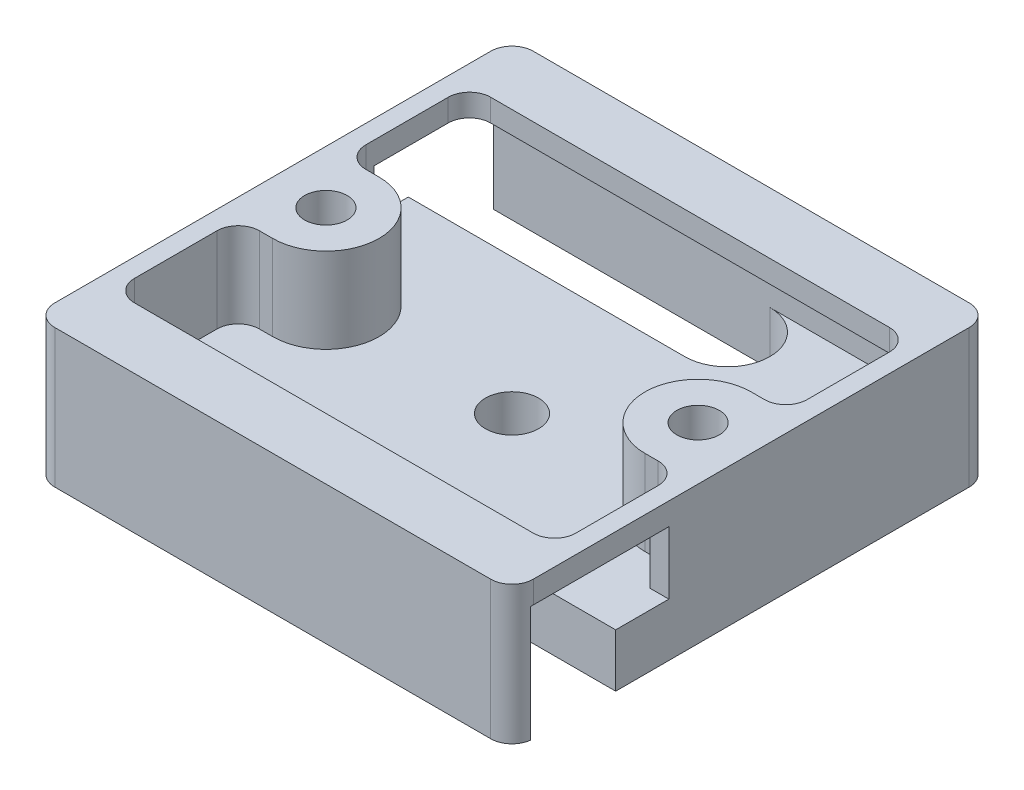
SolidWorks part; units mm, degrees
material "ABS PC"
ref_plane "Alzado" through (0, 0, 0) normal (0, 0, 1) x (1, 0, 0)
ref_plane "Planta" through (0, 0, 0) normal (0, 1, 0) x (1, 0, 0)
ref_plane "Vista lateral" through (0, 0, 0) normal (1, 0, 0) x (0, 0, -1)
sketch "Croquis1" plane through (0, 0, 0) normal (0, 1, 0) x (1, 0, 0)
  line L0 (22.5, -16.75) -> (-3.5, -16.75) construction
  line L1 (-18.5, -18.5) -> (18.5, -18.5) construction
  line L2 (-18.5, -18.5) -> (-18.5, 18.5) construction
  line L3 (-18.5, 18.5) -> (18.5, 18.5) construction
  line L4 (18.5, -18.5) -> (18.5, 18.5) construction
  line L5 (-18.5, -18.5) -> (18.5, 18.5) construction
  line L6 (-18.5, 18.5) -> (18.5, -18.5) construction
  line L7 (-20.75, -20.75) -> (20.75, -20.75) construction
  line L8 (-20.75, -20.75) -> (-20.75, 20.75) construction
  line L9 (-20.75, 20.75) -> (20.75, 20.75) construction
  line L10 (20.75, -20.75) -> (20.75, 20.75) construction
  line L11 (-20.75, -20.75) -> (20.75, 20.75) construction
  line L12 (-20.75, 20.75) -> (20.75, -20.75) construction
  line L13 (-22.5, -22.5) -> (22.5, -22.5)
  line L14 (-22.5, -22.5) -> (-22.5, 22.5)
  line L15 (-22.5, 22.5) -> (22.5, 22.5)
  line L16 (22.5, -22.5) -> (22.5, 22.5)
  line L17 (-22.5, -22.5) -> (22.5, 22.5) construction
  line L18 (-22.5, 22.5) -> (22.5, -22.5) construction
  line L19 (22.5, -20.75) -> (-3.5, -20.75)
  line L20 (22.5, -12.75) -> (-3.5, -12.75)
  line L21 (-7.5, 0) -> (-7.5, -16.75) construction
  line L22 (-22.5, 16.75) -> (3.5, 16.75) construction
  line L23 (-22.5, 20.75) -> (3.5, 20.75)
  line L24 (-22.5, 12.75) -> (3.5, 12.75)
  line L25 (7.5, 16.75) -> (7.5, 0) construction
  line L26 (-3.5, -20.75) -> (-20.75, -20.75)
  line L27 (-20.75, -20.75) -> (-20.75, 7.75)
  line L28 (3.5, 20.75) -> (20.75, 20.75)
  line L29 (20.75, 20.75) -> (20.75, -7.75)
  line L30 (-20.75, 7.75) -> (-22.5, 7.75)
  line L31 (20.75, -7.75) -> (22.5, -7.75)
  circle A0 centre (0, 0) radius 7.5 construction
  arc A1 (22.5, -20.75) -> (22.5, -12.75) centre (22.5, -16.75) ccw
  arc A2 (-3.5, -12.75) -> (-3.5, -20.75) centre (-3.5, -16.75) ccw
  arc A3 (-22.5, 20.75) -> (-22.5, 12.75) centre (-22.5, 16.75) ccw
  arc A4 (3.5, 12.75) -> (3.5, 20.75) centre (3.5, 16.75) ccw
  circle A5 centre (0, 0) radius 2.5
  point P0 (0, 0)
  point P5 (0, 0)
  point P19 (9.5, -16.75)
  point P28 (-9.5, 16.75)
  dimension "D7" = 4
  dimension "D8" = 15
  dimension "D12" = 5
  dimension "D1" = 37
  dimension "D2" = 37
  dimension "D3" = 2.25
  dimension "D4" = 2.25
  dimension "D5" = 45
  dimension "D6" = 45
  dimension "D9" = 1.75
  dimension "D10" = 5
  dimension "D11" = 5
extrude "Saliente-Extruir1" add sketch "Croquis1" against normal blind 5 contours L27 L30 L14 L13 L16 L19 L26 | A4 L24 L14 L30 L27 L26 A2 L20 L16 L31 L29 L28 A0 | L29 L31 L16 L15 L14 L23 L28 region at (-21.9578, 0, 7.375) region at (-21.8879, 0, -10.25) region at (-21.9578, 0, -21.625)
extrude "Saliente-Extruir2" add sketch "Croquis1<3>" along normal blind 6 contours L27 L30 L14 L13 L16 L19 L26 | L29 L31 L16 L15 L14 L23 L28 region at (-21.9578, 0, 7.375) region at (-21.9578, 0, -21.625)
sketch "Croquis1<3>" plane through (0, 0, 0) normal (0, 1, 0) x (1, 0, 0) same geometry as "Croquis1"
sketch "Croquis2" plane through (0, 6, 0) normal (0, 1, 0) x (1, 0, 0)
  line L12 (-22.5, 22.5) -> (22.5, 22.5)
  line L33 (22.5, 22.5) -> (22.5, -22.5)
  line L34 (22.5, -22.5) -> (-22.5, -22.5)
  line L35 (-22.5, -22.5) -> (-22.5, 22.5)
  line L37 (-20.75, -20.75) -> (-20.75, 7.75) construction
  line L38 (-20.75, -22.5) -> (-20.75, 22.5)
  line L40 (20.75, 22.5) -> (20.75, -22.5)
  line L41 (20.75, 20.75) -> (20.75, -7.75) construction
  line L42 (-20.75, 16.75) -> (20.75, 16.75)
  line L43 (20.75, -16.75) -> (-20.75, -16.75)
  line L44 (22.5, -20.75) -> (-20.75, -20.75) construction
  line L45 (-22.5, 20.75) -> (20.75, 20.75) construction
  line M9 (-20.75, -20.75) -> (-20.75, 7.75)
  line M10 (-20.75, 7.75) -> (-22.5, 7.75)
  line M11 (-22.5, 7.75) -> (-22.5, -22.5)
  line M12 (-22.5, -22.5) -> (22.5, -22.5)
  line M13 (22.5, -22.5) -> (22.5, -20.75)
  line M14 (22.5, -20.75) -> (-20.75, -20.75)
  dimension "D1" = 4
  dimension "D2" = 4
extrude "Saliente-Extruir5" add sketch "Croquis2" along normal blind 2 and the other way blind 0.1 contours L38 L42 L40 L12 | L38 L12 L35 M10 | L40 L43 M9 M14 | L40 L38 L34 M14 | L38 M12 M9 M10 M11 | L12 L40 L33 M14 | L40 M14 M12 M13 region at (-21.625, 6, -15.125) region at (0, 6, -19.625) region at (-21.625, 6, 7.375) region at (21.625, 6, -0.875) region at (0, 6, 21.625) region at (0, 6, 18.75) region at (21.625, 6, 21.625)
sketch "Croquis3" plane through (0, 8, 0) normal (0, 1, 0) x (1, 0, 0)
  line L0 (-22.5, -22.5) -> (-22.5, 22.5) construction
  line L1 (-22.5, -5) -> (-17.5, -5)
  line L2 (-22.5, -5) -> (-22.5, 5)
  line L3 (-22.5, 5) -> (-17.5, 5)
  line L4 (-17.5, -5) -> (-17.5, 5)
  line L5 (0, 22.5) -> (0, -22.5) construction
  line L6 (-22.5, 22.5) -> (22.5, 22.5) construction
  line L7 (-22.5, -22.5) -> (22.5, -22.5) construction
  line L8 (-22.5, 0) -> (20.75, 0) construction
  line L9 (20.75, 20.75) -> (20.75, -7.75) construction
  arc A0 (-17.5, 5) -> (-17.5, -5) centre (-17.5, 0) cw
  circle A1 centre (-17.5, 0) radius 2
  point P19 (-12.5, 0)
  line M7 (-20.75, -16.75) -> (-20.75, 16.75)
  dimension "D3" = 4
  dimension "D2" = 5
  dimension "D1" = 10
extrude "Saliente-Extruir6" add sketch "Croquis3" against normal up to surface (8 mm away) contours A1 L4 L3 L1 M7 | A1 L4 A0 | L4 A1 | L4 A1 region at (-20.6449, 8, 0) region at (-15.1354, 8, 0) region at (-18.3488, 8, 0) region at (-16.6512, 8, 0) up to face at (0, 0, 2.5)
extrude "Cortar-Extruir1" cut sketch "Croquis3<3>" against normal up to next contours L4 A1 | L4 A1 region at (-18.3488, 8, 0) region at (-16.6512, 8, 0)
sketch "Croquis3<3>" plane through (0, 8, 0) normal (0, 1, 0) x (1, 0, 0) same geometry as "Croquis3"
mirror "Simetría1" about plane through (0, 0, 0) normal (1, 0, 0) of "Saliente-Extruir6", "Cortar-Extruir1"
sketch "Croquis4" plane through (0, -5, 0) normal (0, -1, 0) x (1, 0, 0)
  circle A0 centre (17.5, 0) radius 2 construction
  circle A1 centre (-17.5, 0) radius 2 construction
  circle A2 centre (17.5, 0) radius 2
  circle A3 centre (-17.5, 0) radius 2
  circle A4 centre (-17.5, 0) radius 3.0002
  circle A5 centre (17.5, 0) radius 3
  dimension "D1" = 1.0002
  dimension "D2" = 1
  dimension "D4" = 6.0005
  dimension "D5" = 4
  dimension "D3" = 35
extrude "Cortar-Extruir2" cut sketch "Croquis4" against normal blind 2
fillet "Redondeo1" radius 2 8 edges at (-20.75, 4, -5) (-20.75, 4, 5) (20.75, 4, 5) (20.75, 4, -5) (20.75, 6.95, -16.75) (-20.75, 6.95, 16.75) (-20.75, 6.95, -16.75) (20.75, 6.95, 16.75)
fillet "Redondeo2" radius 2 6 edges at (-22.5, 1.5, -22.5) (22.5, 1.5, -22.5) (-22.5, 1.5, 22.5) (22.5, 1.5, 22.5) (20.75, 2.95, -20.75) (-20.75, 2.95, 20.75)
equation "\"D2@Croquis1\"=\"D1@Croquis1\""
equation "\"D6@Croquis1\"=\"D5@Croquis1\""
